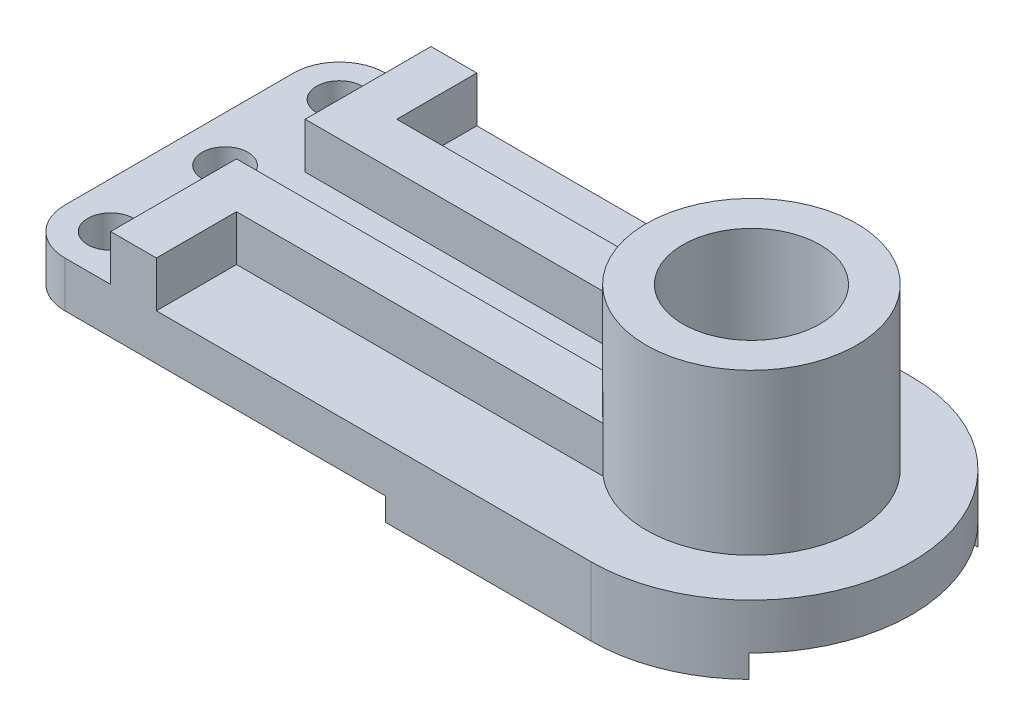
SolidWorks part; units mm, degrees
ref_plane "前视基准面" through (0, 0, 0) normal (0, 0, 1) x (1, 0, 0)
ref_plane "上视基准面" through (0, 0, 0) normal (0, 1, 0) x (1, 0, 0)
ref_plane "右视基准面" through (0, 0, 0) normal (1, 0, 0) x (0, 0, -1)
other "Configuration Table"
sketch "草图1" plane through (0, 0, 0) normal (0, 1, 0) x (1, 0, 0)
  line L1 (0, 35) -> (-115, 35)
  line L2 (-125, 25) -> (-125, -25)
  line L3 (-115, -35) -> (0, -35)
  line L4 (-105, 7.5) -> (-21.7428, 7.5)
  line L5 (-105, 35) -> (-95, 35)
  line L6 (-105, 35) -> (-105, 7.5)
  line L8 (-95, 35) -> (-95, 17.5)
  line L11 (-95, 17.5) -> (-14.9248, 17.5)
  line L13 (-125, 0) -> (0, 0) construction
  line L14 (-105, -35) -> (-105, -7.5)
  line L15 (-105, -35) -> (-95, -35)
  line L16 (-95, -35) -> (-95, -17.5)
  line L17 (-95, -17.5) -> (-14.9248, -17.5)
  line L19 (-105, -7.5) -> (-21.7428, -7.5)
  line L21 (-110.6699, -2.5) -> (-70, -2.5)
  line L23 (-110.6699, 2.5) -> (-70, 2.5)
  line L24 (-70, -2.5) -> (-70, 2.5)
  arc A0 (0, -35) -> (0, 35) centre (0, 0) ccw
  circle A1 centre (-115, 25) radius 5
  circle A2 centre (-115, -25) radius 5
  arc A3 (-110.6699, 2.5) -> (-110.6699, -2.5) centre (-115, 0) ccw
  arc A4 (-125, -25) -> (-115, -35) centre (-115, -25) ccw
  arc A5 (-115, 35) -> (-125, 25) centre (-115, 25) ccw
  circle A6 centre (0, 0) radius 15
  circle A7 centre (0, 0) radius 17.5
  circle A8 centre (0, 0) radius 23
  point P5 (0, 0)
  point P32 (-125, -35)
  point P35 (-125, 35)
  dimension "D1" = 35
  dimension "D2" = 70
  dimension "D7" = 10
  dimension "D8" = 5
  dimension "D11" = 10
  dimension "D14" = 35
  dimension "D15" = 30
  dimension "D16" = 46
  dimension "D3" = 115
  dimension "D4" = 10
  dimension "D5" = 15
  dimension "D6" = 5
  dimension "D9" = 50
  dimension "D10" = 45
  dimension "D12" = 10
  dimension "D13" = 95
extrude "凸台-拉伸1" add sketch "草图1" along normal blind 10 contours A8 L17 L16 L3 A0 L1 L8 L11 | L13 L2 A4 L3 L14 L19 A8 L24 L21 A3 A2 | L2 L13 A3 L23 L24 A8 L4 L6 L1 A5 A1 region at (33.5235, 0, 0) region at (-106.0903, 0, -21.25) region at (-110, 0, 33.9097)
extrude "凸台-拉伸2" add sketch "草图1<3>" along normal blind 20 contours A8 L11 L8 L1 L6 L4 | A8 L19 L14 L3 L16 L17 region at (-68.402, 0, -14.8784) region at (-68.402, 0, 14.8784)
sketch "草图1<3>" plane through (0, 0, 0) normal (0, 1, 0) x (1, 0, 0) same geometry as "草图1"
extrude "凸台-拉伸3" add sketch "草图1<4>" along normal blind 45 contours A8 A7 | A7 A6 region at (9.3641, 0, -20.2932) region at (-17.005, 0, 0)
sketch "草图1<4>" plane through (0, 0, 0) normal (0, 1, 0) x (1, 0, 0) same geometry as "草图1"
extrude "切除-拉伸1" cut sketch "草图1<5>" along normal blind 5 contours A7 | A6
sketch "草图1<5>" plane through (0, 0, 0) normal (0, 1, 0) x (1, 0, 0) same geometry as "草图1"
sketch "草图2" plane through (0, 0, 0) normal (0, -1, 0) x (1, 0, 0)
  line L0 (-115, 35) -> (0, 35) construction
  line L1 (-45, 35) -> (0, 35)
  line L2 (-45, 35) -> (-45, 25)
  line L3 (-45, 25) -> (24.4949, 25)
  line L5 (0, 0) -> (-37.0106, 0) construction
  line L7 (-45, -25) -> (24.4949, -25)
  line L8 (-45, -35) -> (-45, -25)
  line L9 (-45, -35) -> (0, -35)
  arc A0 (0, -35) -> (0, 35) centre (0, 0) ccw construction
  arc A1 (0, -35) -> (24.4949, -25) centre (0, 0) ccw
  arc A2 (24.4949, 25) -> (0, 35) centre (0, 0) ccw
  dimension "D1" = 50
  dimension "D2" = 45
extrude "凸台-拉伸4" add sketch "草图2" along normal blind 5
